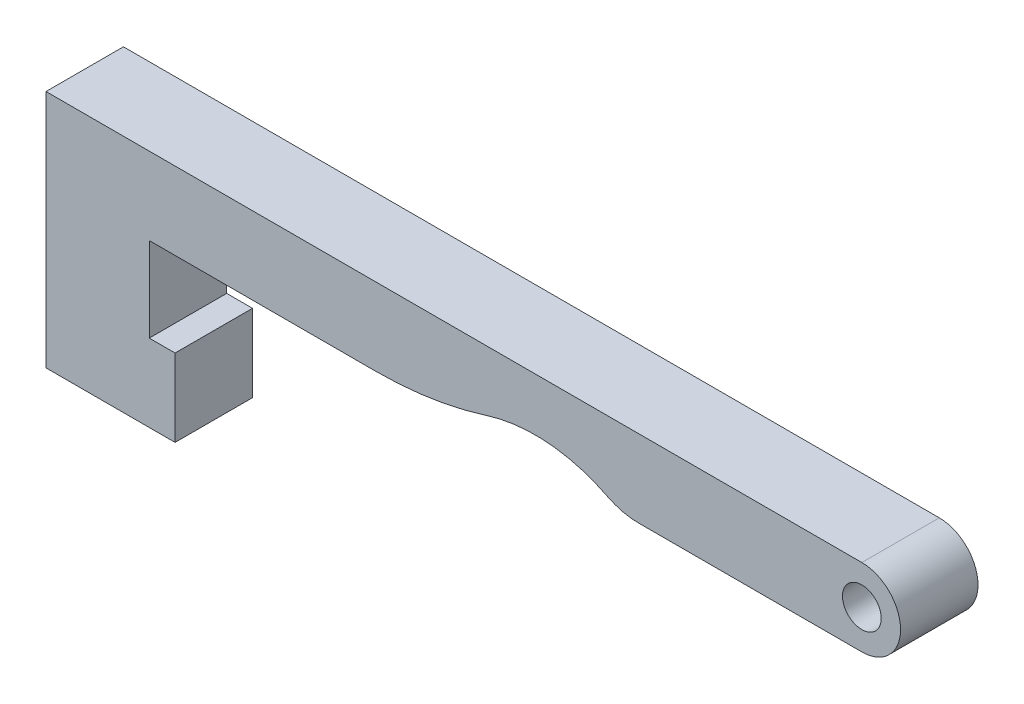
SolidWorks part; units mm, degrees
ref_plane "Front Plane" through (0, 0, 0) normal (0, 0, 1) x (1, 0, 0)
ref_plane "Top Plane" through (0, 0, 0) normal (0, 1, 0) x (1, 0, 0)
ref_plane "Right Plane" through (0, 0, 0) normal (1, 0, 0) x (0, 0, -1)
sketch "Sketch1" plane through (0, 0, 0) normal (0, 0, 1) x (1, 0, 0)
  line L0 (50, 0) -> (0, 0)
  line L1 (0, 0) -> (0, 92.7342)
  line L2 (0, 92.7342) -> (316.0534, 92.7342)
  line L4 (316.0534, 62.7342) -> (229.5566, 62.7342)
  line L5 (127.8211, 62.7342) -> (40, 62.7342)
  line L6 (40, 62.7342) -> (40, 30)
  line L7 (40, 30) -> (50, 30)
  line L8 (50, 30) -> (50, 0)
  arc A0 (229.5566, 62.7342) -> (217.6166, 65.5822) centre (229.5566, 89.1869) cw
  arc A1 (217.6166, 65.5822) -> (170.6837, 69.3706) centre (189.5126, 10.0223) ccw
  arc A2 (170.6837, 69.3706) -> (127.8211, 62.7342) centre (127.8211, 204.4725) cw
  circle A3 centre (316.0534, 77.7342) radius 7.5
  arc A4 (316.0534, 62.7342) -> (316.0534, 92.7342) centre (316.0534, 77.7342) ccw
  point P13 (429.3295, 78.2849)
  point P17 (331.6015, 68.301)
  point P18 (130.7954, 57.5113)
  point P19 (155.8041, 57.5113)
  point P20 (230.3615, 66.5385)
  point P21 (263.2672, 62.3937)
  point P22 (237.9359, 69.6813)
  point P25 (230.8302, 75.5375)
  point P26 (277.6616, 59.5292)
  point P27 (381.425, 77.1536)
  point P28 (218.9558, 68.2455)
  point P29 (316.0534, 77.8802)
  point P30 (127.8211, 62.7342)
  dimension "D5" = 15
  dimension "D6" = 30
  dimension "D1" = 40
  dimension "D2" = 10
  dimension "D3" = 30
  dimension "D4" = 30
extrude "Boss-Extrude1" add sketch "Sketch1" along normal blind 30
